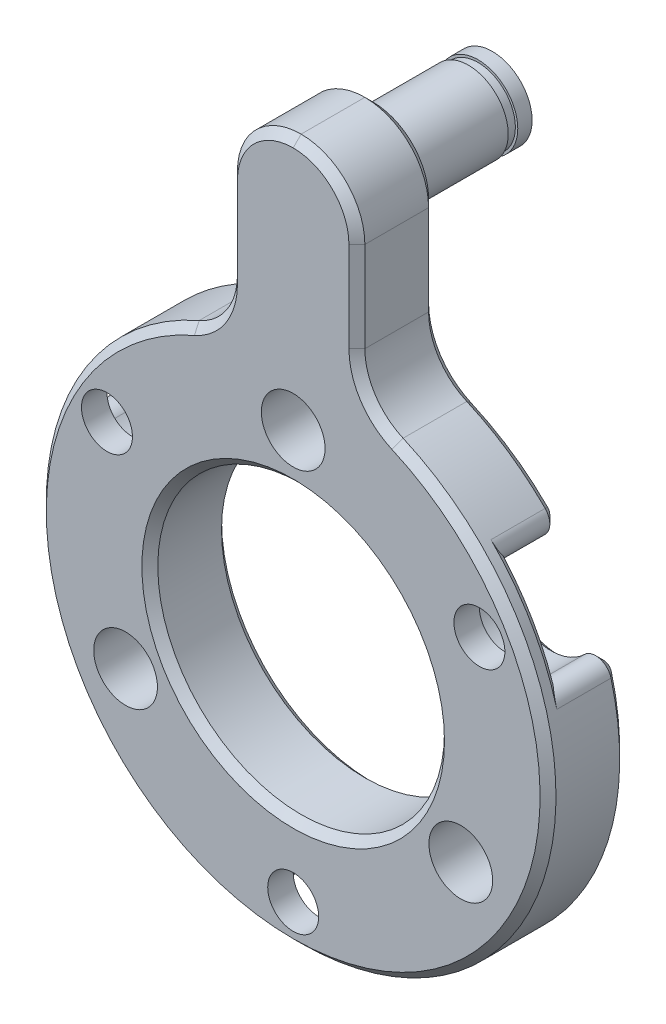
SolidWorks part; units mm, degrees
material "1.0503 (C45)"
ref_plane "前视基准面" through (0, 0, 0) normal (0, 0, 1) x (1, 0, 0)
ref_plane "上视基准面" through (0, 0, 0) normal (0, 1, 0) x (1, 0, 0)
ref_plane "右视基准面" through (0, 0, 0) normal (1, 0, 0) x (0, 0, -1)
other "Configuration Table"
sketch "草图1" plane through (0, 0, 0) normal (0, 0, 1) x (1, 0, 0)
  circle A0 centre (0, 0) radius 16
  dimension "D1" = 32
extrude "凸台-拉伸1" add sketch "草图1" along normal mid plane 5
sketch "草图2" plane through (0, 0, 2.5) normal (0, 0, 1) x (1, 0, 0)
  circle A0 centre (0, 0) radius 12.15
  point P0 (0, 12.15)
  point P15 (10.5222, -6.075)
  point P16 (-10.5222, -6.075)
  dimension "D1" = 24.3
  dimension "D2" = 3
hole_wizard "Ø4.0mm 暗销孔1" positions "草图2" profile "草图3" hole size "Ø4.0" standard "GB"
sketch "草图3" plane through (0, 12.15, 2.5) normal (1, 0, 0) x (0, -1, 0)
  line L0 (0, 0) -> (0, 4.2017)
  line L1 (0, 4.2017) -> (2, 3)
  line L2 (2, 3) -> (2, 0)
  line L5 (2, 0) -> (0, 0)
  line L10 (0, 4.2017) -> (-2, 3) construction
  line L11 (0, -6.35) -> (0, 107.95) construction
  dimension "孔直径" = 4
  dimension "孔深度" = 3
  dimension "导头角度" = 118
sketch "草图4" plane through (0, 0, -2.5) normal (0, 0, -1) x (-1, 0, 0)
  circle A0 centre (0, 0) radius 13.5
  point P0 (0, -13.5)
  point P14 (-11.6913, 6.75)
  point P15 (11.6913, 6.75)
  dimension "D1" = 27
  dimension "D2" = 3
hole_wizard "M3 六角圆柱头螺钉的柱形沉头孔1" positions "草图4" profile "草图5" counterbore size "M3" standard "GB" end condition up to next
sketch "草图5" plane through (0, -13.5, -2.5) normal (1, 0, 0) x (0, 1, 0)
  line L0 (0, 0) -> (0, 5)
  line L1 (0, 5) -> (1.6, 5)
  line L3 (1.6, 5) -> (1.6, 3.4)
  line L4 (1.6, 3.4) -> (3, 3.4)
  line L5 (3, 3.4) -> (3, 0)
  line L7 (3, 0) -> (0, 0)
  line L11 (0, -6.35) -> (0, 107.95) construction
  dimension "通孔孔直径" = 3.2
  dimension "通孔孔深度" = 5
  dimension "柱形沉头孔直径" = 6
  dimension "柱形沉头孔深度" = 3.4
fillet "圆角1" radius 1 6 edges at (14.6694, 6.3881, -0.8) (12.867, 9.5101, -0.8) (-14.6694, 6.3881, -0.8) (-12.867, 9.5101, -0.8) (1.8025, -15.8981, -0.8) (-1.8025, -15.8981, -0.8)
sketch "草图6" plane through (0, 0, -2.5) normal (0, 0, -1) x (-1, 0, 0)
  circle A0 centre (0, 24) radius 2.5
  dimension "D1" = 5
  dimension "D2" = 24
extrude "凸台-拉伸2" add sketch "草图6" along normal blind 7.5
sketch "草图9" plane through (0, 0, -2.5) normal (0, 0, -1) x (-1, 0, 0)
  line L0 (0, 30.4507) -> (0, -2.4734) construction
  line L1 (-4, 15.4919) -> (-4, 28)
  line L2 (-4, 28) -> (4, 28)
  line L3 (4, 28) -> (4, 15.4919)
  arc A2 (11.3191, 11.3083) -> (-11.3191, 11.3083) centre (0, 0) ccw construction
  arc A4 (4, 15.4919) -> (-4, 15.4919) centre (0, 0) ccw
  circle A6 centre (0, 24) radius 2.5
  circle A7 centre (0, 24) radius 2.5 construction
  dimension "D1" = 0
  dimension "D2" = 8
  dimension "D3" = 4
extrude "凸台-拉伸3" add sketch "草图9" against normal up to surface (5 mm away) up to face at (1.6, -13.5, 2.5)
sketch "草图7" plane through (0, 0, -2.5) normal (0, 0, -1) x (-1, 0, 0)
  circle A0 centre (0, 0) radius 9
  dimension "D1" = 18
extrude "切除-拉伸1" cut sketch "草图7" against normal through all
ref_plane "基准面1" through (0, 0, -8.5) normal (0, 0, -1) x (-1, 0, 0)
sketch "草图8" plane through (0, 0, -8.5) normal (0, 0, -1) x (-1, 0, 0)
  circle A0 centre (0, 24) radius 2.35
  circle A2 centre (0, 24) radius 2.5
  circle A3 centre (0, 24) radius 2.5
  dimension "D1" = 4.7
  dimension "D2" = 0
extrude "切除-拉伸2" cut sketch "草图8" along normal blind 0.6
fillet "圆角3" radius 4 4 edges at (4, 28, 0) (-4, 28, 0) (-4, 15.4919, 0) (4, 15.4919, 0)
chamfer "倒角1" distance 0.5 angle 45 31 edges at (-9, 0, -2.5) (-9, 0, 2.5) (0, -16, 0.9) (13.8564, 8, 0.9) (-13.8564, 8, 0.9) (0, -16, 2.5) (9.0933, 5.25, -2.5) (11.579, 10.348, -2.5) (14.7512, 4.8537, -2.5) (9.0171, 13.2171, -2.5) (13.8564, -8, -2.5) (3.1722, -15.2017, -2.5) (0, -10.5, -2.5) (-3.1722, -15.2017, -2.5) (-9.0171, 13.2171, -2.5) (-13.8564, -8, -2.5) (-11.579, 10.348, -2.5) (-14.7512, 4.8537, -2.5) (-9.0933, 5.25, -2.5) (-2.8284, 26.8284, 2.5) (2.8284, 26.8284, 2.5) (-4, 21.1652, 2.5) (4, 21.1652, 2.5) (-4.6534, 16.1394, 2.5) (4.6534, 16.1394, 2.5) (4.6534, 16.1394, -2.5) (4, 21.1652, -2.5) (2.8284, 26.8284, -2.5) (-2.8284, 26.8284, -2.5) (-4, 21.1652, -2.5) (-4.6534, 16.1394, -2.5)
